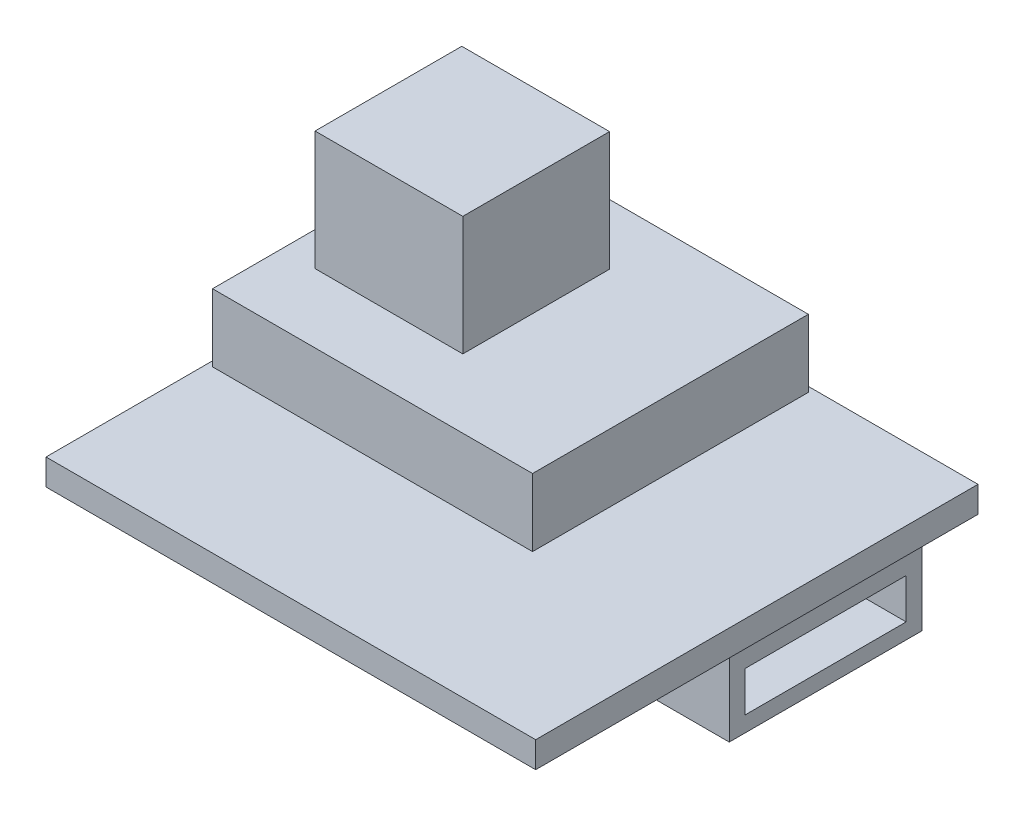
SolidWorks part; units mm, degrees
ref_plane "Front Plane" through (0, 0, 0) normal (0, 0, 1) x (1, 0, 0)
ref_plane "Top Plane" through (0, 0, 0) normal (0, 1, 0) x (1, 0, 0)
ref_plane "Right Plane" through (0, 0, 0) normal (1, 0, 0) x (0, 0, -1)
sketch "Sketch1" plane through (0, 0, 0) normal (0, 1, 0) x (1, 0, 0)
  line L1 (0, 0) -> (23.9014, 0)
  line L2 (0, 0) -> (0, 21.59)
  line L3 (0, 21.59) -> (23.9014, 21.59)
  line L4 (23.9014, 0) -> (23.9014, 21.59)
  dimension "D1" = 23.9014
  dimension "D2" = 21.59
extrude "Boss-Extrude1" add sketch "Sketch1" along normal blind 1.27
sketch "Sketch2" plane through (0, 1.27, 0) normal (0, 1, 0) x (1, 0, 0)
  line L0 (23.9014, 21.59) -> (0, 21.59) construction
  line L1 (0.254, 21.336) -> (15.875, 21.336)
  line L2 (0.254, 21.336) -> (0.254, 7.874)
  line L3 (0.254, 7.874) -> (15.875, 7.874)
  line L4 (15.875, 21.336) -> (15.875, 7.874)
  line L5 (0, 21.59) -> (0, 0) construction
  dimension "D1" = 15.621
  dimension "D2" = 13.462
  dimension "D3" = 0.254
  dimension "D4" = 0.254
extrude "Boss-Extrude2" add sketch "Sketch2" along normal blind 3.302
sketch "Sketch3" plane through (0, 4.572, 0) normal (0, 1, 0) x (1, 0, 0)
  line L0 (15.875, 21.336) -> (0.254, 21.336) construction
  line L1 (1.905, 18.3896) -> (9.1186, 18.3896)
  line L2 (1.905, 18.3896) -> (1.905, 11.2268)
  line L3 (1.905, 11.2268) -> (9.1186, 11.2268)
  line L4 (9.1186, 18.3896) -> (9.1186, 11.2268)
  line L5 (0.254, 21.336) -> (0.254, 7.874) construction
  dimension "D1" = 7.2136
  dimension "D2" = 7.1628
  dimension "D3" = 2.9464
  dimension "D4" = 1.651
extrude "Boss-Extrude3" add sketch "Sketch3" along normal blind 5.8166
sketch "Sketch4" plane through (0, 0, 0) normal (0, -1, 0) x (-1, 0, 0)
  line L0 (-23.9014, 0) -> (-23.9014, 21.59) construction
  line L1 (-8.6614, 9.8298) -> (-12.8524, 9.8298)
  line L2 (-8.6614, 9.8298) -> (-8.6614, 16.8656)
  line L3 (-8.6614, 16.8656) -> (-12.8524, 16.8656)
  line L4 (-12.8524, 9.8298) -> (-12.8524, 16.8656)
  line L5 (-23.9014, 21.59) -> (0, 21.59) construction
  dimension "D1" = 4.191
  dimension "D2" = 7.0358
  dimension "D3" = 15.24
  dimension "D4" = 11.7602
extrude "Boss-Extrude4" add sketch "Sketch4" along normal blind 4.5212
sketch "Sketch5" plane through (0, 0, 0) normal (0, -1, 0) x (-1, 0, 0)
  line L1 (-19.0754, 9.7028) -> (-23.6474, 9.7028)
  line L2 (-19.0754, 9.7028) -> (-19.0754, 19.1008)
  line L3 (-19.0754, 19.1008) -> (-23.6474, 19.1008)
  line L4 (-23.6474, 9.7028) -> (-23.6474, 19.1008)
  line L5 (-23.9014, 21.59) -> (0, 21.59) construction
  line L6 (-23.9014, 0) -> (-23.9014, 21.59) construction
  dimension "D1" = 4.572
  dimension "D2" = 9.398
  dimension "D3" = 11.8872
  dimension "D4" = 0.254
extrude "Boss-Extrude5" add sketch "Sketch5" along normal blind 3.81
sketch "Sketch6" plane through (23.6474, 0, 0) normal (1, 0, 0) x (0, 0, -1)
  line L0 (9.7028, -3.81) -> (9.7028, 0) construction
  line L1 (10.4648, -1.0861) -> (18.3388, -1.0861)
  line L2 (10.4648, -1.0861) -> (10.4648, -3.048)
  line L3 (10.4648, -3.048) -> (18.3388, -3.048)
  line L4 (18.3388, -1.0861) -> (18.3388, -3.048)
  line L6 (9.7028, -2.5654) -> (10.4648, -2.5654) construction
  line L7 (9.7028, -0.3241) -> (19.1008, -0.3241) construction
  line L8 (18.3388, -2.2879) -> (19.1008, -2.2879) construction
  line L9 (19.1008, -3.81) -> (19.1008, 0) construction
  line L10 (16.5812, -3.048) -> (16.5812, -3.81) construction
  line L11 (19.1008, -3.81) -> (9.7028, -3.81) construction
  line L12 (13.3211, -0.3241) -> (13.3211, -1.0861) construction
  dimension "D1" = 0.762
extrude "Cut-Extrude1" cut sketch "Sketch6" against normal offset from surface (3.81 mm away) 0.762 up to face at (19.0754, -1.905, -14.4018)
